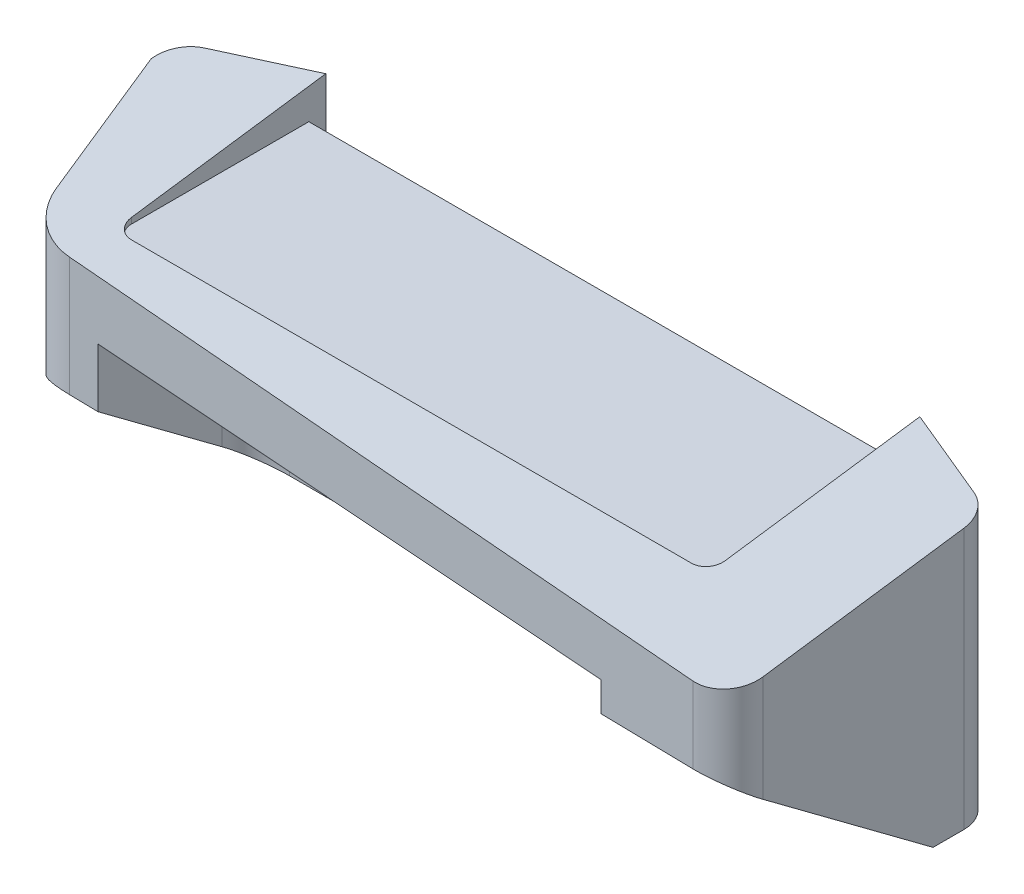
SolidWorks part; units mm, degrees
material "6061 Alloy"
ref_plane "Top Plane" through (0, 0, 0) normal (0, 0, 1) x (1, 0, 0)
ref_plane "Front Plane" through (0, 0, 0) normal (0, 1, 0) x (1, 0, 0)
ref_plane "Right Plane" through (0, 0, 0) normal (1, 0, 0) x (0, 0, -1)
other "Center of Mass"
sketch "Sketch1" plane through (0, 0, 0) normal (0, 0, 1) x (1, 0, 0)
  line L0 (-60, -20) -> (-60, 20)
  line L1 (-60, -20) -> (60, -20)
  line L2 (-60, 20) -> (60, 20)
  line L3 (60, -20) -> (60, 20)
  line L4 (-60, -20) -> (60, 20) construction
  line L5 (-60, 20) -> (60, -20) construction
  point P1 (0, 0)
  dimension "D1" = 120
  dimension "D2" = 40
extrude "Billet" add sketch "Sketch1" along normal blind 50
sketch "Sketch9" plane through (-60, 0, 0) normal (-1, 0, 0) x (0, 0, 1)
  line L0 (0, 20) -> (52.5206, 20)
  line L1 (52.5206, 20) -> (52.5206, 12.6187)
  line L2 (52.5206, 12.6187) -> (0, 20)
  dimension "D1" = 52.5206
  dimension "D2" = 172
extrude "Cut-Extrude3" cut sketch "Sketch9" against normal through all
ref_plane "Right Angle to Bottom Face Edge" through (0, 20, 0) normal (0, 1, 0) x (1, 0, 0)
sketch "Sketch10" plane through (0, 20, 0) normal (0, 1, 0) x (1, 0, 0)
  line L0 (-60, 0) -> (-60, -1.5)
  line L1 (0, 0) -> (0, -50) construction
  line L2 (60, 0) -> (60, -1.5)
  line L4 (-60, -50) -> (60, -50)
  line L5 (60, -50) -> (60, 0)
  line L6 (60, 0) -> (-60, 0)
  line L7 (-60, 0) -> (-60, -50)
  line L8 (-60, -50) -> (60, -50)
  line L9 (60, -50) -> (60, 0)
  line L10 (60, 0) -> (-60, 0)
  line L11 (-60, 0) -> (-60, -50)
  arc A0 (-60, -1.5) -> (60, -1.5) centre (0, -1200.75) cw
  dimension "D2" = 1.5
  dimension "D1" = 0
extrude "Bottom Bevel" cut sketch "Sketch10" against normal through all contours L0 A0 L10 | L10 A0 L2 region at (-45.0019, 20, 0.45) region at (45.0019, 20, 0.45)
sketch "Sketch11" plane through (0, 20, 0) normal (0, 1, 0) x (1, 0, 0)
  line L0 (-60, 0) -> (-60, -7)
  line L2 (-60, -1.5) -> (-60, -50) construction
  line L3 (-60, -7) -> (-41.7644, 0)
  line L4 (-41.7644, 0) -> (-60, 0)
  line L5 (0, 0) -> (0, -50) construction
  line L6 (-60, -50) -> (60, -50) construction
  line L7 (0, 0) -> (-57.8395, 0) construction
  line L8 (-60, -50) -> (-60, 10.8249) construction
  line L9 (60, -7) -> (41.7644, 0)
  line L10 (60, 0) -> (60, -7)
  line L11 (41.7644, 0) -> (60, 0)
  arc A0 (60, -1.5) -> (-60, -1.5) centre (0, -1200.75) ccw construction
  dimension "D1" = 7
  dimension "D2" = 69
extrude "Heel and Toe Relief" cut sketch "Sketch11" against normal through all contours L4 L0 L3 | L9 L11 L10
fillet "Heel and Toe Fillet" radius 5 2 edges at (-60, -0.4919, 7) (60, -0.4919, 7)
sketch "Sketch13" plane through (0, 0, 50) normal (0, 0, 1) x (1, 0, 0)
  line L0 (-60, -20) -> (60, -20) construction
  line L1 (-40, -20) -> (40, -20)
  line L2 (-40, -20) -> (-40, 5.996)
  line L3 (-40, 5.996) -> (40, 5.996)
  line L4 (40, -20) -> (40, 5.996)
  line L5 (-60, 12.973) -> (60, 12.973) construction
  dimension "D1" = 80
  dimension "D2" = 40
  dimension "D3" = 6.977
extrude "Body Cavity" cut sketch "Sketch13" against normal blind 35
fillet "Body Cavity Fillets" radius 5 2 edges at (40, -7.002, 15) (-40, -7.002, 15)
ref_plane "Plane2" through (0, -20, 0) normal (0, -1, 0) x (-1, 0, 0)
sketch "Sketch14" plane through (0, -20, 0) normal (0, -1, 0) x (-1, 0, 0)
  line L0 (60, -50) -> (60, -10.4364) construction
  line L2 (60, -15) -> (-60, -15)
  line L3 (60, -15) -> (60, -65)
  line L4 (60, -65) -> (-60, -65)
  line L5 (-60, -15) -> (-60, -65)
  line L6 (-35, -15) -> (35, -15) construction
  point P6 (0, -15)
  dimension "D1" = 120
  dimension "D2" = 50
revolve "Back Angle" cut sketch "Sketch14" angle 36.675 about L2 reverse direction yes
sketch "Sketch15" plane through (0, 20, 0) normal (0, 1, 0) x (1, 0, 0)
  line L0 (-60, -10.4364) -> (-47.25, -50)
  line L1 (-47.25, -50) -> (-60, -50)
  line L5 (-43.851, -0.801) -> (-56.7918, -5.7685)
  line L6 (-60, -10.4364) -> (-60, -50)
  line L7 (-60, -50) -> (60, -50)
  line L8 (60, -50) -> (60, -10.4364)
  line L9 (56.7918, -5.7685) -> (43.851, -0.801)
  line L11 (-60, -10.4364) -> (-60, -50)
  arc A3 (-56.7918, -5.7685) -> (-60, -10.4364) centre (-55, -10.4364) ccw
  arc A4 (60, -10.4364) -> (56.7918, -5.7685) centre (55, -10.4364) ccw
  arc A5 (43.851, -0.801) -> (-43.851, -0.801) centre (0, -1200.75) ccw
  dimension "D2" = 12.75
  dimension "D1" = 0
extrude "Heel Relief" cut sketch "Sketch15" against normal through all
sketch "Sketch16" plane through (0, 20, 0) normal (0, 1, 0) x (1, 0, 0)
  line L5 (60, -45.5) -> (-51.2948, -37.4488)
  line L6 (-51.2948, -37.4488) -> (-47.25, -50)
  line L7 (60, -45.5) -> (60, -50)
  line L8 (-60, -10.4364) -> (-47.25, -50) construction
  line L9 (60, -10.4364) -> (60, -50) construction
  line L10 (-60, -10.4364) -> (-47.25, -50)
  line L11 (-47.25, -50) -> (60, -50)
  line L12 (60, -50) -> (60, -10.4364)
  line L13 (56.7918, -5.7685) -> (43.851, -0.801)
  line L14 (-43.851, -0.801) -> (-56.7918, -5.7685)
  line L16 (-47.25, -50) -> (60, -50)
  arc A6 (-56.7918, -5.7685) -> (-60, -10.4364) centre (-55, -10.4364) ccw
  arc A7 (60, -10.4364) -> (56.7918, -5.7685) centre (55, -10.4364) ccw
  arc A8 (43.851, -0.801) -> (-43.851, -0.801) centre (0, -1200.75) ccw
  dimension "D2" = 68
  dimension "D3" = 4.5
  dimension "D1" = 0
extrude "Cut-Extrude4" cut sketch "Sketch16" against normal through all
fillet "Fillet1" radius 10 1 edges at (-51.2948, 5.7273, 37.4488)
fillet "Fillet2" radius 5 1 edges at (60, 8.1593, 45.5)
sketch "Sketch17" plane through (0, 20, 0) normal (0, 1, 0) x (1, 0, 0)
  line L0 (-43.851, 0) -> (-43.851, -32)
  line L1 (-43.851, -32) -> (43.851, -32)
  line L2 (43.851, -32) -> (43.851, 0)
  line L3 (43.851, 0) -> (-43.851, 0)
  point P3 (0, 0)
  dimension "D1" = 32
extrude "Face Insert" cut sketch "Sketch17" against normal blind 5
fillet "Fillet3" radius 2.5 2 edges at (-43.851, 15.2513, 32) (43.851, 15.2513, 32)
sketch "Sketch18" plane through (0, 15, 0) normal (0, 1, 0) x (1, 0, 0)
  line L0 (-43.851, -0.801) -> (-43.851, -3.301)
  line L1 (-43.851, -0.801) -> (-43.851, -29.5) construction
  line L2 (-43.851, -3.301) -> (43.851, -3.301)
  line L3 (-43.851, -0.801) -> (-43.851, -29.5)
  line L4 (-41.351, -32) -> (41.351, -32)
  line L5 (43.851, -29.5) -> (43.851, -0.801)
  line L9 (43.851, -0.801) -> (43.851, -29.5) construction
  line L10 (43.851, -3.301) -> (43.851, -0.801)
  arc A3 (-43.851, -29.5) -> (-41.351, -32) centre (-41.351, -29.5) ccw
  arc A4 (41.351, -32) -> (43.851, -29.5) centre (41.351, -29.5) ccw
  arc A5 (43.851, -0.801) -> (-43.851, -0.801) centre (0, -1200.75) ccw
  arc A8 (43.851, -0.801) -> (-43.851, -0.801) centre (0, -1200.75) ccw
  dimension "D2" = 2.5
  dimension "D1" = 0
extrude "Cut-Extrude6" cut sketch "Sketch18" against normal through all
sketch "Sketch19" plane through (0, 0, 15) normal (0, 0, 1) x (1, 0, 0)
  point P0 (5, -8.504)
  point P3 (-25, -8.504)
hole_wizard "M5x0.8 Tapped Hole1" positions "Sketch19" profile "Sketch20" tap size "M5x0.8" standard "ANSI Metric" end condition through all
cosmetic thread "Hole Thread1" parameters "D2"=5
cosmetic thread "Hole Thread2" parameters "D2"=5
sketch "Sketch20" plane through (5, -8.504, 15) normal (1, 0, 0) x (0, -1, 0)
  line L0 (0, 0) -> (0, 14.199)
  line L1 (0, 14.199) -> (2.1, 14.199)
  line L2 (2.1, 14.199) -> (2.1, 0)
  line L5 (2.1, 0) -> (0, 0)
  line L11 (0, -6.35) -> (0, 107.95) construction
  dimension "Thru Tap Drill Dia." = 4.2
  dimension "Thru Tap Drill Depth" = 14.199
sketch "Sketch21" plane through (0, 0, 3.301) normal (0, 0, -1) x (-1, 0, 0)
  point P0 (-33.8, 0.1)
  point P3 (33.8, 0.1)
hole_wizard "M5x0.8 Tapped Hole2" positions "Sketch21" profile "Sketch22" tap size "M5x0.8" standard "ANSI Metric"
sketch "Sketch22" plane through (33.8, 0.1, 3.301) normal (1, 0, 0) x (0, 1, 0)
  line L0 (0, 0) -> (0, 9.2618)
  line L1 (0, 9.2618) -> (2.1, 8)
  line L2 (2.1, 8) -> (2.1, 0)
  line L5 (2.1, 0) -> (0, 0)
  line L10 (0, 9.2618) -> (-2.1, 8) construction
  line L11 (0, -6.35) -> (0, 107.95) construction
  dimension "Tap Drill Dia." = 4.2
  dimension "Tap Drill Depth" = 8
  dimension "Drill Angle" = 118
cosmetic thread "Hole Thread3" parameters "D1"=10, "D2"=5
cosmetic thread "Hole Thread4" parameters "D1"=10, "D2"=5
